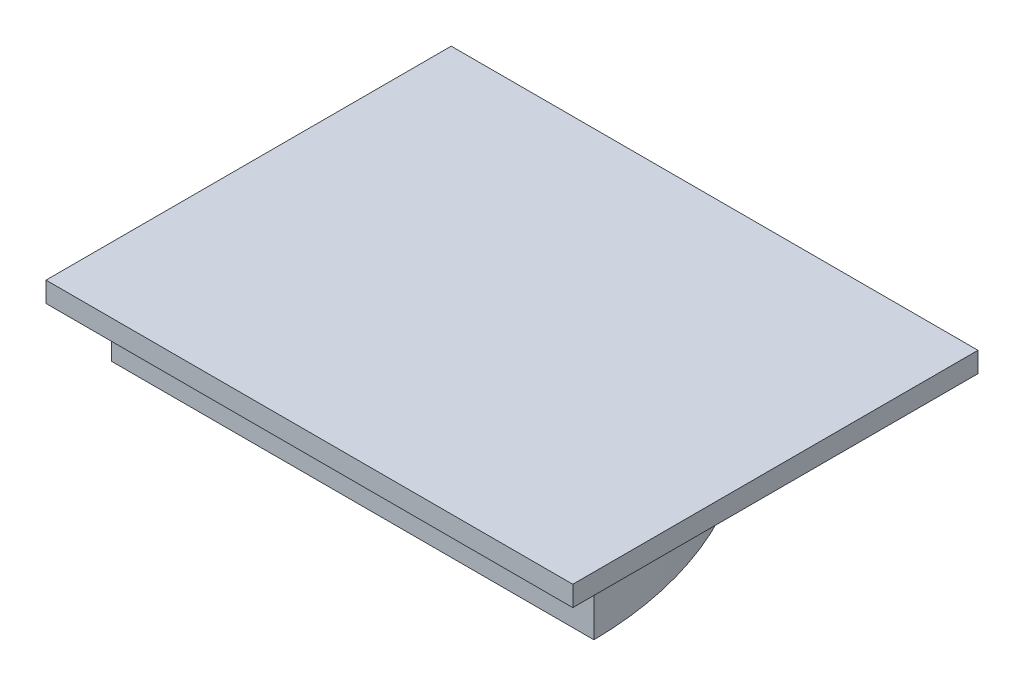
SolidWorks part; units mm, degrees
ref_plane "Front Plane" through (0, 0, 0) normal (0, 0, 1) x (1, 0, 0)
ref_plane "Top Plane" through (0, 0, 0) normal (0, 1, 0) x (1, 0, 0)
ref_plane "Right Plane" through (0, 0, 0) normal (1, 0, 0) x (0, 0, -1)
sketch "Sketch1" plane through (0, 0, 0) normal (0, 1, 0) x (1, 0, 0)
  line L1 (-24.1771, 7.883) -> (-0.3771, 7.883)
  line L2 (-24.1771, 7.883) -> (-24.1771, -10.117)
  line L3 (-24.1771, -10.117) -> (-0.3771, -10.117)
  line L4 (-0.3771, 7.883) -> (-0.3771, -10.117)
  dimension "D1" = 18
  dimension "D2" = 23.8
extrude "Boss-Extrude1" add sketch "Sketch1" along normal blind 3
fillet "Fillet1" radius 18.2 2 edges at (-24.1771, 1.5, -7.883) (-0.3771, 1.5, -7.883)
sketch "Sketch2" plane through (0, 3, 0) normal (0, 1, 0) x (1, 0, 0)
  line L0 (-12.2771, 6.7582) -> (-12.2771, -10.117) construction
  line L1 (-24.1771, -10.117) -> (-0.3771, -10.117) construction
  line L3 (-25.2771, 7.738) -> (0.7229, 7.738)
  line L4 (-25.2771, 7.738) -> (-25.2771, -12.262)
  line L5 (-25.2771, -12.262) -> (0.7229, -12.262)
  line L6 (0.7229, 7.738) -> (0.7229, -12.262)
  line L7 (-25.2771, 7.738) -> (0.7229, -12.262) construction
  line L8 (-25.2771, -12.262) -> (0.7229, 7.738) construction
  point P5 (-12.2771, -2.262)
  point P10 (-12.2771, -2.262)
  dimension "D1" = 20
  dimension "D2" = 26
extrude "Boss-Extrude2" add sketch "Sketch2" along normal blind 1
